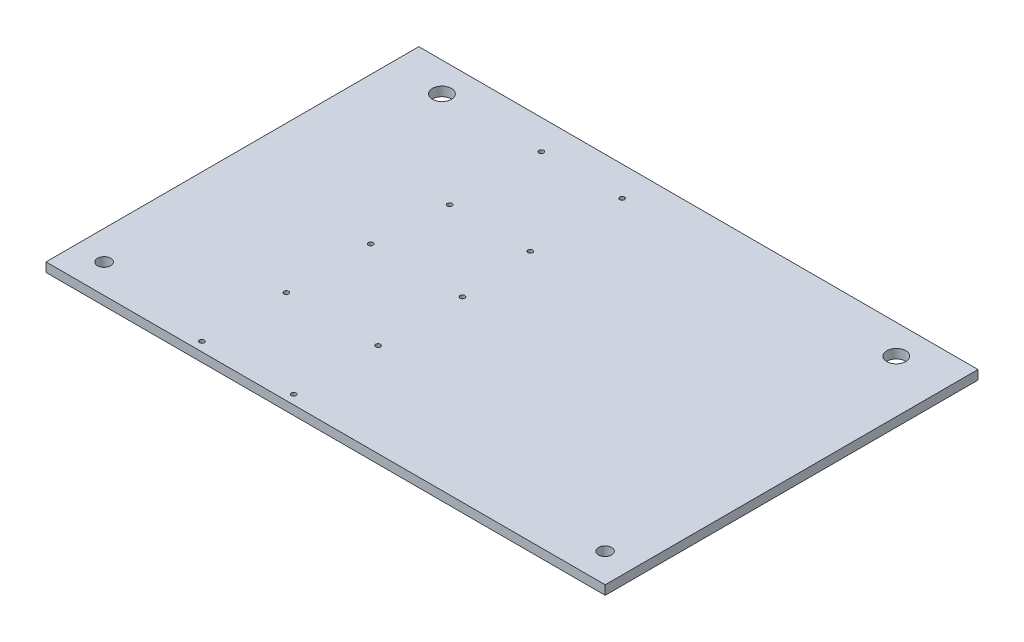
SolidWorks part; units mm, degrees
ref_plane "Front Plane" through (0, 0, 0) normal (0, 0, 1) x (1, 0, 0)
ref_plane "Top Plane" through (0, 0, 0) normal (0, 1, 0) x (1, 0, 0)
ref_plane "Right Plane" through (0, 0, 0) normal (1, 0, 0) x (0, 0, -1)
sketch "Sketch1" plane through (0, 0, 0) normal (0, 1, 0) x (1, 0, 0)
  line L1 (0, 0) -> (304.8, 0)
  line L2 (0, 0) -> (0, -203.2)
  line L3 (0, -203.2) -> (304.8, -203.2)
  line L4 (304.8, 0) -> (304.8, -203.2)
  dimension "D1" = 203.2
  dimension "D2" = 304.8
extrude "Boss-Extrude1" add sketch "Sketch1" along normal blind 5
sketch "Sketch2" plane through (0, 5, 0) normal (0, 1, 0) x (1, 0, 0)
  line L0 (152.4, 0) -> (152.4, -203.2) construction
  line L1 (304.8, 0) -> (0, 0) construction
  line L2 (0, -203.2) -> (304.8, -203.2) construction
  line L3 (0, -101.6) -> (304.8, -101.6) construction
  line L4 (0, 0) -> (0, -203.2) construction
  line L5 (304.8, -203.2) -> (304.8, 0) construction
  circle A2 centre (288.925, -187.4139) radius 3.2639
  circle A3 centre (15.875, -187.4139) radius 3.2639
  circle A4 centre (28.575, -15.9639) radius 3.2639
  circle A5 centre (276.225, -15.9639) radius 3.2639
  dimension "D1" = 85.8139
  dimension "D4" = 6.5278
  dimension "D7" = 171.45
  dimension "D3" = 247.65
  dimension "D2" = 12.7
  dimension "D5" = 85.8139
  dimension "D6" = 273.05
sketch "locations for led holes" plane through (0, 5, 0) normal (0, 1, 0) x (1, 0, 0)
  line L1 (0, -203.2) -> (304.8, -203.2) construction
  line L2 (0, 0) -> (0, -203.2) construction
  point P0 (80, -198.2)
  point P1 (80, -152.2)
  point P2 (80, -106.2)
  point P3 (130, -106.2)
  point P4 (130, -152.2)
  point P5 (130, -198.2)
  dimension "D1" = 46
  dimension "D2" = 46
  dimension "D3" = 50
  dimension "D4" = 5
  dimension "D5" = 80
hole_wizard "clearance holes for led panel" positions "Sketch4" profile "Sketch5" hole size "M2" standard "ISO" end condition through all
sketch "Sketch4" plane through (0, 5, 0) normal (0, 1, 0) x (1, 0, 0)
  point P0 (80, -106.2)
  point P3 (130, -106.2)
  point P6 (130, -152.2)
  point P9 (80, -152.2)
  point P12 (80, -198.2)
  point P15 (130, -198.2)
sketch "Sketch5" plane through (80, 5, 106.2) normal (1, 0, 0) x (0, 0, 1)
  line L0 (0, 0) -> (0, 5)
  line L1 (0, 5) -> (1.3, 5)
  line L2 (1.3, 5) -> (1.3, 0)
  line L5 (1.3, 0) -> (0, 0)
  line L11 (0, -6.35) -> (0, 107.95) construction
  dimension "Thru Hole Dia." = 2.6
  dimension "Thru Hole Depth" = 5
sketch "location of holes for solar mount" plane through (0, 5, 0) normal (0, 1, 0) x (1, 0, 0)
  circle A1 centre (83, -16.2) radius 1.2 construction
  circle A2 centre (83, -16.2) radius 1.2
  circle A3 centre (127, -16.2) radius 1.2 construction
  circle A4 centre (127, -16.2) radius 1.2
  circle A5 centre (127, -66.2) radius 1.2 construction
  circle A6 centre (127, -66.2) radius 1.2
  circle A7 centre (83, -66.2) radius 1.2 construction
  circle A8 centre (83, -66.2) radius 1.2
hole_wizard "1/4 Clearance Hole1" positions "Sketch9" profile "Sketch10" hole size "1/4" standard "ANSI Inch" end condition through all
sketch "Sketch9" plane through (0, 5, 0) normal (0, 1, 0) x (1, 0, 0)
  point P0 (15.875, -187.4139)
  point P3 (288.925, -187.4139)
sketch "Sketch10" plane through (15.875, 5, 187.4139) normal (1, 0, 0) x (0, 0, 1)
  line L0 (0, 0) -> (0, 5)
  line L1 (0, 5) -> (3.5712, 5)
  line L2 (3.5712, 5) -> (3.5712, 0)
  line L5 (3.5712, 0) -> (0, 0)
  line L11 (0, -6.35) -> (0, 107.95) construction
  dimension "Thru Hole Dia." = 7.1425
  dimension "Thru Hole Depth" = 5
hole_wizard "3/8 Clearance Hole1" positions "Sketch15" profile "Sketch16" hole size "3/8" standard "ANSI Inch" end condition through all
sketch "Sketch15" plane through (0, 5, 0) normal (0, 1, 0) x (1, 0, 0)
  point P0 (28.575, -15.9639)
  point P3 (276.225, -15.9639)
sketch "Sketch16" plane through (28.575, 5, 15.9639) normal (1, 0, 0) x (0, 0, 1)
  line L0 (0, 0) -> (0, 5)
  line L1 (0, 5) -> (5.1587, 5)
  line L2 (5.1587, 5) -> (5.1587, 0)
  line L5 (5.1587, 0) -> (0, 0)
  line L11 (0, -6.35) -> (0, 107.95) construction
  dimension "Thru Hole Dia." = 10.3175
  dimension "Thru Hole Depth" = 5
extrude "Cut-Extrude1" cut sketch "location of holes for solar mount" against normal up to surface (5 mm away) up to face at (28.575, 0, 21.1226)
hole_wizard "M2 Clearance Hole1" positions "Sketch17" profile "Sketch18" hole size "M2" standard "ISO" end condition through all
sketch "Sketch17" plane through (0, 5, 0) normal (0, 1, 0) x (1, 0, 0)
  point P4 (127, -16.2)
  point P7 (127, -66.2)
  point P10 (83, -66.2)
  point P15 (83, -16.2)
  point P21 (0, 0)
sketch "Sketch18" plane through (127, 5, 16.2) normal (1, 0, 0) x (0, 0, 1)
  line L0 (0, 0) -> (0, 5)
  line L1 (0, 5) -> (1.3, 5)
  line L2 (1.3, 5) -> (1.3, 0)
  line L5 (1.3, 0) -> (0, 0)
  line L11 (0, -6.35) -> (0, 107.95) construction
  dimension "Thru Hole Dia." = 2.6
  dimension "Thru Hole Depth" = 5
